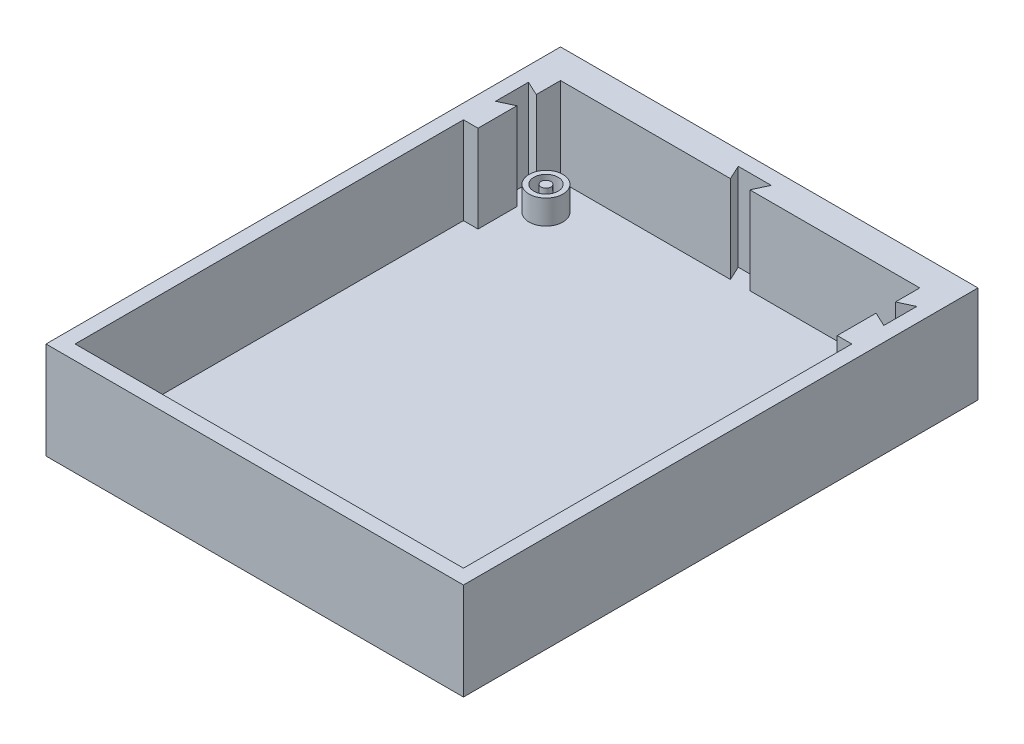
SolidWorks part; units mm, degrees
ref_plane "Front Plane" through (0, 0, 0) normal (0, 0, 1) x (1, 0, 0)
ref_plane "Top Plane" through (0, 0, 0) normal (0, 1, 0) x (1, 0, 0)
ref_plane "Right Plane" through (0, 0, 0) normal (1, 0, 0) x (0, 0, -1)
sketch "Sketch1" plane through (0, 0, 0) normal (0, 1, 0) x (1, 0, 0)
  line L1 (0, 0) -> (101.6, 0)
  line L2 (0, 0) -> (0, 127)
  line L3 (0, 127) -> (101.6, 127)
  line L4 (101.6, 0) -> (101.6, 127)
  dimension "D1" = 127
  dimension "D2" = 101.6
extrude "Base Extrude" add sketch "Sketch1" along normal blind 2.54
sketch "Sketch2" plane through (0, 0, 0) normal (0, -1, 0) x (1, 0, 0)
  line L1 (0, 0) -> (101.6, 0)
  line L2 (0, 0) -> (0, -127)
  line L3 (0, -127) -> (101.6, -127)
  line L4 (101.6, 0) -> (101.6, -127)
  line L5 (-3.81, 3.81) -> (105.41, 3.81)
  line L6 (-3.81, 3.81) -> (-3.81, -130.81)
  line L7 (-3.81, -130.81) -> (105.41, -130.81)
  line L8 (105.41, 3.81) -> (105.41, -130.81)
  dimension "D1" = 3.81
  dimension "D2" = 3.81
  dimension "D3" = 3.81
  dimension "D4" = 3.81
extrude "Walls" add sketch "Sketch2" against normal blind 25.4
sketch "Sketch3" plane through (0, 25.4, 0) normal (0, 1, 0) x (1, 0, 0)
  line L0 (101.6, 127) -> (101.6, 0) construction
  line L1 (0, 127) -> (101.6, 127)
  line L2 (0, 127) -> (0, 101.6)
  line L3 (0, 101.6) -> (3.81, 101.6)
  line L4 (101.6, 127) -> (101.6, 101.6)
  line L5 (0, 118.6166) -> (3.81, 116.84)
  line L6 (3.81, 101.6) -> (3.81, 111.76)
  line L7 (3.81, 111.76) -> (0, 109.9834)
  line L8 (0, 127) -> (0, 0) construction
  line L9 (3.81, 116.84) -> (3.81, 123.19)
  line L10 (3.81, 123.19) -> (48.26, 123.19)
  line L11 (48.26, 123.19) -> (46.4834, 127)
  line L12 (46.4834, 127) -> (55.1166, 127)
  line L13 (55.1166, 127) -> (53.34, 123.19)
  line L14 (53.34, 123.19) -> (97.79, 123.19)
  line L15 (97.79, 123.19) -> (97.79, 116.84)
  line L16 (97.79, 116.84) -> (101.6, 118.6166)
  line L17 (101.6, 118.6166) -> (101.6, 109.9834)
  line L18 (101.6, 109.9834) -> (97.79, 111.76)
  line L19 (97.79, 111.76) -> (97.79, 101.6)
  line L20 (97.79, 101.6) -> (101.6, 101.6)
  line L21 (101.6, 0) -> (101.6, 127) construction
  line L22 (3.81, 116.84) -> (3.81, 111.76) construction
  line L23 (48.26, 123.19) -> (53.34, 123.19) construction
  point P11 (3.81, 114.3)
  point P26 (50.8, 123.19)
  point P29 (0, 0)
  point P31 (50.8, 127)
  line M17 (0, 0) -> (0, 127)
  line M18 (0, 127) -> (101.6, 127)
  line M19 (101.6, 127) -> (101.6, 0)
  dimension "D1" = 115
  dimension "D2" = 3.81
  dimension "D3" = 25.4
  dimension "D4" = 12.7
  dimension "D5" = 5.08
  dimension "D6" = 5.08
  dimension "D7" = 3.81
extrude "Button Guide" add sketch "Sketch3" against normal up to surface (22.86 mm away) contours L6 L7 L3 M17 | L10 L11 L2 L5 L9 M18 | L15 L16 L13 L14 M19 M18 | L19 L20 L18 M19 region at (99.6342, 25.4, -106.25) region at (80.1526, 25.4, -124.6026) region at (1.9658, 25.4, -106.25) region at (21.4474, 25.4, -124.6026) up to face at (50.8, 2.54, -63.5)
sketch "Sketch4" plane through (0, 2.54, 0) normal (0, 1, 0) x (1, 0, 0)
  line L0 (-3.81, 130.81) -> (105.41, 130.81) construction
  line L1 (-3.81, -3.81) -> (-3.81, 130.81) construction
  line L2 (105.41, 130.81) -> (105.41, -3.81) construction
  circle A0 centre (8.89, 114.3) radius 1.27
  circle A1 centre (92.71, 114.3) radius 1.27
  circle A2 centre (8.89, 114.3) radius 3.175
  circle A3 centre (8.89, 114.3) radius 4.445
  circle A4 centre (92.71, 114.3) radius 3.175
  circle A5 centre (92.71, 114.3) radius 4.445
  point P14 (0, 0)
  dimension "D1" = 2.54
  dimension "D6" = 6.35
  dimension "D7" = 8.89
  dimension "D2" = 16.51
  dimension "D3" = 12.7
  dimension "D4" = 12.7
extrude "Spring Guides" add sketch "Sketch4" along normal blind 6.35 contours A3 A2 | A0 | A1 | A5 A4 region at (8.89, 2.54, -114.3) region at (92.71, 2.54, -114.3) region at (4.5707, 2.54, -114.3) region at (88.3907, 2.54, -114.3)
